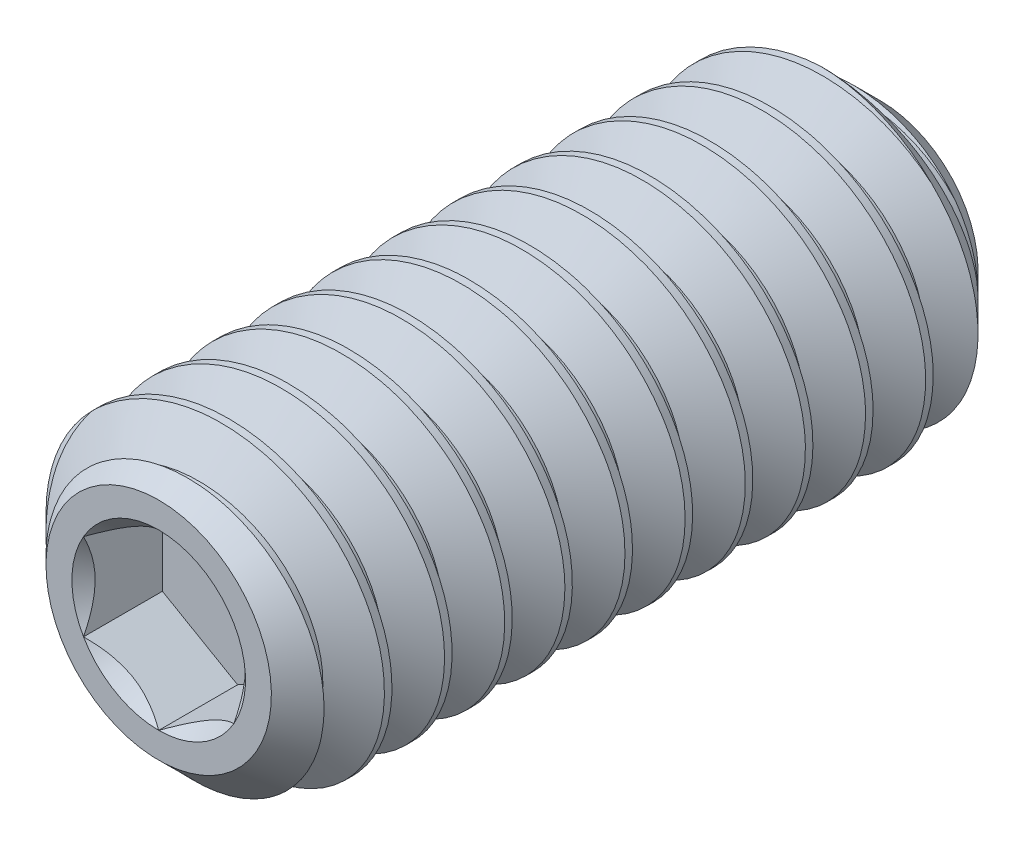
SolidWorks part; units mm, degrees
ref_plane "Front Plane" through (0, 0, 0) normal (0, 0, 1) x (1, 0, 0)
ref_plane "Top Plane" through (0, 0, 0) normal (0, 1, 0) x (1, 0, 0)
ref_plane "Right Plane" through (0, 0, 0) normal (1, 0, 0) x (0, 0, -1)
sketch "Sketch1" plane through (0, 0, 0) normal (1, 0, 0) x (0, 0, -1)
  line L6 (-4.7625, 0) -> (4.7625, 0) construction
  line L7 (-4.7625, 0) -> (-4.7625, 2.0828)
  line L8 (-4.7625, 2.0828) -> (4.7625, 2.0828)
  line L9 (4.7625, 2.0828) -> (4.7625, 0)
  line L10 (4.7129, 2.1687) -> (5.1098, 1.4813) construction
  line L15 (5.1098, 1.4813) -> (5.5066, 2.1687) construction
  line L16 (5.5066, 2.1687) -> (4.7129, 2.1687) construction
  line L17 (4.7377, 2.1258) -> (5.4818, 2.1258)
  line L18 (5.4818, 2.1258) -> (5.1594, 1.5672)
  line L19 (5.1594, 1.5672) -> (5.0602, 1.5672)
  line L20 (5.0602, 1.5672) -> (4.7377, 2.1258)
  line L21 (5.1098, 1.5672) -> (5.1098, 1.4813) construction
  line L22 (4.7625, 2.0828) -> (5.457, 2.0828) construction
  line L23 (5.1098, 2.1687) -> (5.1098, 2.0828) construction
  line L24 (3.9688, 2.0828) -> (4.7625, 1.2891)
  line L25 (-4.7625, 1.4875) -> (-4.1672, 2.0828)
  line L26 (4.7625, 1.2394) -> (4.0178, 0)
  line L27 (4.7625, -1.2394) -> (4.0178, 0)
  point P4 (0, 0)
  point P23 (5.1098, 2.1258)
  point P29 (-3.7211, 0)
  point P30 (3.5719, 2.0828)
  point P31 (3.5719, -2.0828)
  point P32 (-4.7625, -2.0828)
  dimension "Length" = 9.525
  dimension "Screw Size Decimal Equivalent" = 4.1656
  dimension "Pitch" = 0.7937
  dimension "D2" = 0.0992
  dimension "D3" = 0.7937
  dimension "D1" = 45
  dimension "D4" = 0.5953
  dimension "D5" = 59
  dimension "D6" = 0.0496
  dimension "D7" = 1.0414
  dimension "D8" = 1.1906
sketch "Sketch10" plane through (0, 0, 0) normal (0, 0, 1) x (1, 0, 0)
  line L1 (0, 1.1457) -> (-0.9922, 0.5728)
  line L2 (-0.9922, 0.5728) -> (-0.9922, -0.5728)
  line L3 (-0.9922, -0.5728) -> (0, -1.1457)
  line L4 (0, -1.1457) -> (0.9922, -0.5728)
  line L5 (0.9922, -0.5728) -> (0.9922, 0.5728)
  line L6 (0.9922, 0.5728) -> (0, 1.1457)
  circle A0 centre (0, 0) radius 0.9922 construction
  dimension "Drive Size" = 1.9844
sketch "Sketch2" plane through (0, 0, 0) normal (1, 0, 0) x (0, 0, -1)
  line L10 (4.7625, 1.2394) -> (4.0178, 0) construction
  line L18 (-4.7625, 1.4875) -> (-4.1672, 2.0828) construction
  line L20 (4.7625, 1.2394) -> (4.0178, 0)
  line L21 (-4.7625, 1.4875) -> (-4.1672, 2.0828)
  line L22 (-4.1672, 2.0828) -> (4.7625, 2.0828)
  line L23 (4.7625, 2.0828) -> (4.7625, 1.2394)
  line L24 (4.0178, 0) -> (-4.7625, 0)
  line L25 (-4.7625, 0) -> (-4.7625, 1.4875)
revolve "Revolve1" add sketch "Sketch2" angle 360 about L24
chamfer "Chamfer1" distance 0.7937 angle 45 1 edges at (0, 2.0828, -4.7625)
sketch "Sketch3" plane through (0, 0, 4.7625) normal (0, 0, 1) x (1, 0, 0)
  line L0 (-0.9922, -0.5728) -> (0, -1.1457) construction
  line L7 (-0.9922, 0.5728) -> (-0.9922, -0.5728) construction
  line L8 (0, 1.1457) -> (-0.9922, 0.5728) construction
  line L9 (0.9922, 0.5728) -> (0, 1.1457) construction
  line L10 (0.9922, -0.5728) -> (0.9922, 0.5728) construction
  line L11 (0, -1.1457) -> (0.9922, -0.5728) construction
  line L12 (-0.9922, -0.5728) -> (0, -1.1457)
  line L13 (-0.9922, 0.5728) -> (-0.9922, -0.5728)
  line L14 (0, 1.1457) -> (-0.9922, 0.5728)
  line L15 (0.9922, 0.5728) -> (0, 1.1457)
  line L16 (0.9922, -0.5728) -> (0.9922, 0.5728)
  line L17 (0, -1.1457) -> (0.9922, -0.5728)
extrude "Cut-Extrude1" cut sketch "Sketch3" against normal up to vertex (1.0414 mm away) up to point (0, 0, 3.7211)
sketch "Sketch4" plane through (0, 0, 4.7625) normal (0, 0, 1) x (1, 0, 0)
  circle A1 centre (0, 0) radius 1.1457
extrude "Cut-Extrude2" cut sketch "Sketch4" against normal up to vertex (1.0414 mm away) draft 45 up to point (0, 0, 3.7211)
ref_axis "Center Axis 1" through (0, 0, -1.7801) along (0, 0, 1)
sketch "Sketch7" plane through (0, 0, -4.7625) normal (0, 0, -1) x (-1, 0, 0)
  circle A3 centre (0, 0) radius 2.0828 construction
  circle A4 centre (0, 0) radius 2.0828
curve "Helix/Spiral1" pitch 0.7937 height 10.3267 radius 2.0828 centre (0, 0, -4.7625) axis (0, 0, 1) start towards (0, 1, 0)
sketch "Sketch8" plane through (0, 0, 0) normal (1, 0, 0) x (0, 0, -1)
  line L0 (5.1594, 1.5672) -> (5.0602, 1.5672) construction
  line L1 (5.4818, 2.1258) -> (5.1594, 1.5672) construction
  line L2 (4.7377, 2.1258) -> (5.4818, 2.1258) construction
  line L3 (5.0602, 1.5672) -> (4.7377, 2.1258) construction
  line L4 (5.1594, 1.5672) -> (5.0602, 1.5672)
  line L5 (5.4818, 2.1258) -> (5.1594, 1.5672)
  line L6 (4.7377, 2.1258) -> (5.4818, 2.1258)
  line L7 (5.0602, 1.5672) -> (4.7377, 2.1258)
sweep "Cut-Sweep1" cut profiles "Sketch8" path "Helix/Spiral1"
equation "\"D3@Helix/Spiral1\"=\"Length@Sketch1\"+(\"Pitch@Sketch1\"*1.01)"
equation "\"D4@Helix/Spiral1\"=\"Pitch@Sketch1\""
equation "\"D2@Sketch1\" = \"Pitch@Sketch1\" / 8"
equation "\"D3@Sketch1\"=\"Pitch@Sketch1\""
equation "\"D4@Sketch1\"=\"Pitch@Sketch1\"*0.75"
equation "\"D6@Sketch1\"=\"D2@Sketch1\"/2"
equation "\"D7@Sketch1\"=0.25*\"Screw Size Decimal Equivalent@Sketch1\""
equation "\"D1@Chamfer1\"=\"D3@Sketch1\""
equation "\"D8@Sketch1\"=\"Pitch@Sketch1\"*1.5"
